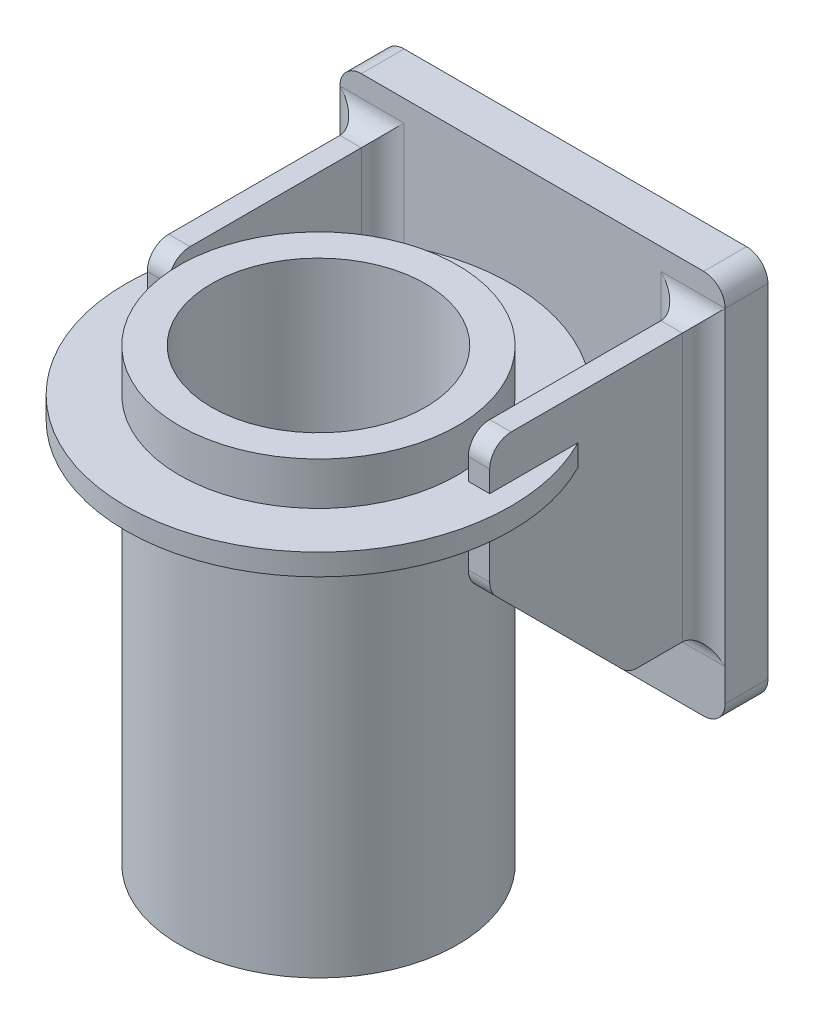
SolidWorks part; units mm, degrees
ref_plane "Front Plane" through (0, 0, 0) normal (0, 0, 1) x (1, 0, 0)
ref_plane "Top Plane" through (0, 0, 0) normal (0, 1, 0) x (1, 0, 0)
ref_plane "Right Plane" through (0, 0, 0) normal (1, 0, 0) x (0, 0, -1)
sketch "Base Sketch" plane through (0, 0, 0) normal (0, 0, 1) x (1, 0, 0)
  line L0 (0, 90) -> (0, -90) construction
  line L1 (-90, -90) -> (90, -90)
  line L2 (-90, -90) -> (-90, 90)
  line L3 (-90, 90) -> (90, 90)
  line L4 (90, -90) -> (90, 90)
  line L5 (-90, -90) -> (90, 90) construction
  line L6 (-90, 90) -> (90, -90) construction
  point P0 (0, 0)
  dimension "D1" = 180
  dimension "D2" = 180
extrude "Base Extrude" add sketch "Base Sketch" against normal blind 20
ref_plane "Support Plane" through (80, 0, 0) normal (1, 0, 0) x (0, 0, -1)
sketch "Support Sketch" plane through (80, 0, 0) normal (1, 0, 0) x (0, 0, -1)
  line L0 (-100, 10) -> (-35, -55)
  line L1 (-100, 70) -> (0, 70)
  line L2 (-100, 70) -> (-100, 10)
  line L3 (-35, -55) -> (0, -55)
  line L4 (0, 70) -> (0, -55)
  line L5 (0, -90) -> (0, 90) construction
  line L6 (0, 90) -> (0, 70) construction
  line L7 (0, -55) -> (0, -90) construction
  line L8 (20, 90) -> (0, 90) construction
  line L9 (20, -90) -> (0, -90) construction
  dimension "D1" = 20
  dimension "D2" = 35
  dimension "D3" = 100
  dimension "D4" = 60
  dimension "D5" = 135
extrude "Support Extrude" add sketch "Support Sketch" against normal blind 10
mirror "Support Mirror" about plane through (0, 0, 0) normal (1, 0, 0) of "Support Extrude"
ref_plane "Cylinder Top Plane" through (0, 50, 0) normal (0, 1, 0) x (1, 0, 0)
sketch "Motor Support Sketch" plane through (0, 50, 0) normal (0, 1, 0) x (1, 0, 0)
  line L0 (-70, -100) -> (-80, -100) construction
  line L1 (-80, -58.7689) -> (-80, -141.2311) construction
  line L2 (-80, 0) -> (-80, -100) construction
  line L3 (-80, -100) -> (-90, -100) construction
  line L4 (-90, 20) -> (-90, 0) construction
  circle A0 centre (0, -100) radius 90
extrude "Motor Support Extrude" add sketch "Motor Support Sketch" against normal blind 10
sketch "Motor Sketch" plane through (0, 40, 0) normal (0, -1, 0) x (1, 0, 0)
  circle A0 centre (0, 100) radius 65
  arc A1 (80, 58.7689) -> (-80, 58.7689) centre (0, 100) ccw construction
  dimension "D1" = 25
extrude "Motor Extrude" add sketch "Motor Sketch" along normal blind 180 and the other way up to surface (30 mm away) other way up to face at (75, 70, 50)
sketch "Motor Hole Sketch" plane through (0, 70, 0) normal (0, 1, 0) x (1, 0, 0)
  circle A0 centre (0, -100) radius 50
  circle A1 centre (0, -100) radius 65 construction
  dimension "D1" = 100
extrude "Motor Hole Cut" cut sketch "Motor Hole Sketch" against normal up to surface (210 mm away) up to face at (0, -140, 35)
fillet "Support Fillets" radius 10 18 edges at (-90, 90, -10) (-90, -90, -10) (90, -90, -10) (90, 90, -10) (75, -55, 35) (75, 10, 100) (75, 70, 100) (-75, -55, 35) (-75, 10, 100) (-75, 70, 100) (-75, -55, 0) (-70, 7.5, 0) (-80, 7.5, 0) (75, -55, 0) (80, 7.5, 0) (70, 7.5, 0) (-75, 70, 0) (75, 70, 0)
